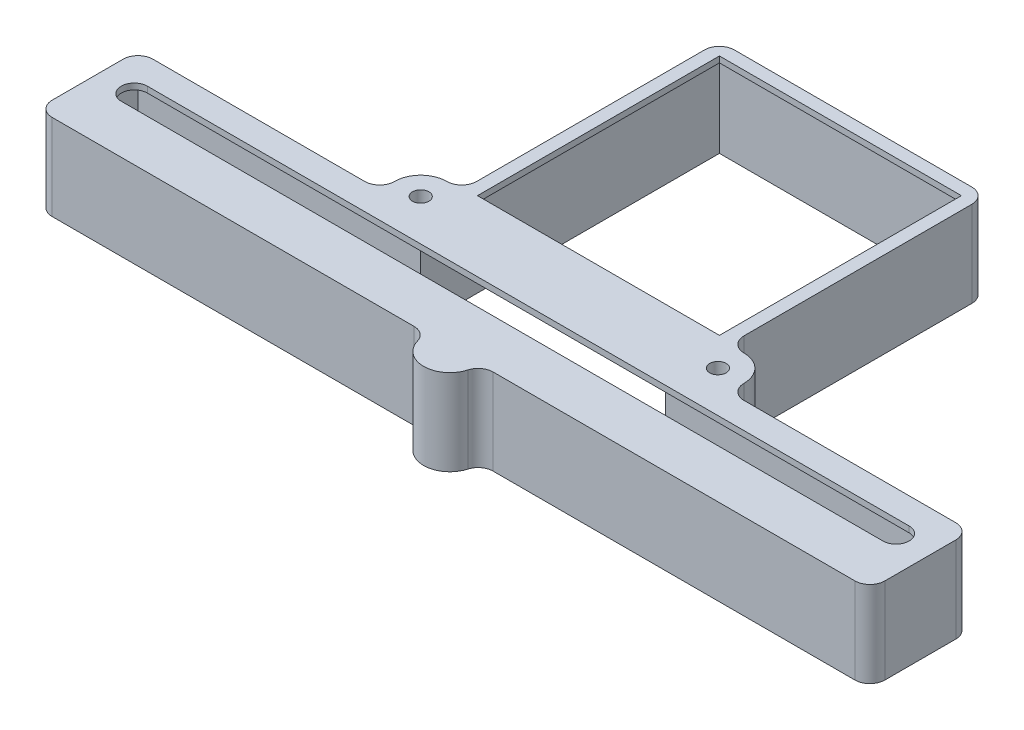
SolidWorks part; units mm, degrees
ref_plane "Front Plane" through (0, 0, 0) normal (0, 0, 1) x (1, 0, 0)
ref_plane "Top Plane" through (0, 0, 0) normal (0, 1, 0) x (1, 0, 0)
ref_plane "Right Plane" through (0, 0, 0) normal (1, 0, 0) x (0, 0, -1)
sketch "Sketch1" plane through (0, 0, 0) normal (0, 1, 0) x (1, 0, 0)
  line L0 (0, 36.3641) -> (0, -33.052) construction
  line L1 (-16.4, 25.25) -> (16.4, 25.25)
  line L2 (-16.4, 25.25) -> (-16.4, -25.25)
  line L3 (-16.4, -25.25) -> (16.4, -25.25)
  line L4 (16.4, 25.25) -> (16.4, -25.25)
  line L5 (-16.4, 25.25) -> (16.4, -25.25) construction
  line L6 (-16.4, -25.25) -> (16.4, 25.25) construction
  line L7 (-16.4, -25.25) -> (-16.4, -26.75) construction
  line L12 (-54.25, -14.75) -> (-55.75, -14.75) construction
  line L13 (-54.25, -14.75) -> (54.25, -14.75)
  line L14 (17.9, -26.75) -> (-17.9, -26.75)
  line L15 (17.9, -26.75) -> (17.9, 26.75)
  line L16 (17.9, 26.75) -> (-17.9, 26.75)
  line L17 (-17.9, -26.75) -> (-17.9, 26.75)
  line L18 (17.9, -26.75) -> (-17.9, 26.75) construction
  line L19 (17.9, 26.75) -> (-17.9, -26.75) construction
  line L20 (-16.4, 25.25) -> (-17.9, 25.25) construction
  line L21 (-16.4, 25.25) -> (-16.4, 26.75) construction
  line L22 (-54.25, -14.75) -> (-54.25, -25.25)
  line L23 (-54.25, -25.25) -> (54.25, -25.25)
  line L24 (54.25, -14.75) -> (54.25, -25.25)
  line L25 (-54.25, -14.75) -> (54.25, -25.25) construction
  line L26 (-54.25, -25.25) -> (54.25, -14.75) construction
  line L27 (-55.75, -13.25) -> (55.75, -13.25)
  line L28 (-55.75, -13.25) -> (-55.75, -26.75)
  line L29 (-55.75, -26.75) -> (55.75, -26.75)
  line L30 (55.75, -13.25) -> (55.75, -26.75)
  line L31 (-55.75, -13.25) -> (55.75, -26.75) construction
  line L32 (-55.75, -26.75) -> (55.75, -13.25) construction
  line L33 (-2, -27.25) -> (-3.5, -27.25) construction
  line L34 (-3.5, -27.25) -> (-3.5, -26.75)
  line L35 (3.5, -27.25) -> (3.5, -26.75)
  line L36 (-2, -27.25) -> (-2, -25.25)
  line L37 (2, -27.25) -> (2, -25.25)
  circle A0 centre (0, -27.25) radius 2
  circle A1 centre (0, -27.25) radius 3.5
  point P0 (0, 0)
  point P7 (0, -20)
  point P11 (0, -20)
  point P13 (0, 0)
  dimension "D6" = 4
  dimension "D1" = 32.8
  dimension "D2" = 50.5
  dimension "D3" = 1.5
  dimension "D4" = 108.5
  dimension "D5" = 10.5
extrude "Boss-Extrude1" add sketch "Sketch1" along normal blind 11.5 contours L17 L16 L15 L14 | L27 L30 L29 L28 | A1
sketch "Sketch2" plane through (0, 11.5, 0) normal (0, 1, 0) x (1, 0, 0)
  line L0 (0, 26.75) -> (0, -30.75) construction
  line L1 (17.9, 26.75) -> (-17.9, 26.75) construction
  line L3 (-16.2, 25.05) -> (-17.9, 25.05) construction
  line L4 (-16.2, -7.35) -> (16.2, -7.35)
  line L5 (-16.2, -7.35) -> (-16.2, 25.05)
  line L6 (-16.2, 25.05) -> (16.2, 25.05)
  line L7 (16.2, -7.35) -> (16.2, 25.05)
  line L8 (-16.2, -7.35) -> (16.2, 25.05) construction
  line L9 (-16.2, 25.05) -> (16.2, -7.35) construction
  line L10 (-17.9, -13.25) -> (-17.9, 26.75) construction
  line L11 (-16.2, 25.05) -> (-16.2, 26.75) construction
  arc A0 (-3.4641, -26.75) -> (3.4641, -26.75) centre (0, -27.25) ccw construction
  point P4 (0, 0)
  point P5 (0, 0)
  point P6 (0, 8.85)
  point P11 (0, -30.75)
  dimension "D1" = 32.4
extrude "Cut-Extrude1" cut sketch "Sketch2" against normal blind 8.7
sketch "Sketch3" plane through (0, 0, 0) normal (0, -1, 0) x (1, 0, 0)
  line L0 (-55.75, 20) -> (55.75, 20) construction
  line L1 (-55.75, 13.25) -> (-55.75, 26.75) construction
  line L2 (55.75, 13.25) -> (55.75, 26.75) construction
  line L3 (0, 30.75) -> (0, -26.75) construction
  line L4 (55.75, 26.75) -> (3.4641, 26.75) construction
  line L5 (17.9, -26.75) -> (-17.9, -26.75) construction
  line L6 (-54.25, 25.25) -> (-55.75, 25.25) construction
  line L7 (-54.25, 25.25) -> (54.25, 25.25)
  line L8 (-54.25, 25.25) -> (-54.25, 14.75)
  line L9 (-54.25, 14.75) -> (54.25, 14.75)
  line L10 (54.25, 25.25) -> (54.25, 14.75)
  line L11 (-54.25, 25.25) -> (54.25, 14.75) construction
  line L12 (-54.25, 14.75) -> (54.25, 25.25) construction
  line L13 (-54.25, 25.25) -> (-54.25, 26.75) construction
  line L14 (-2, 27.25) -> (-2, 25.25)
  line L15 (2, 27.25) -> (2, 25.25)
  arc A0 (3.4641, 26.75) -> (-3.4641, 26.75) centre (0, 27.25) ccw construction
  circle A1 centre (0, 27.25) radius 2
  point P12 (0, 20)
  dimension "D2" = 4
  dimension "D1" = 1.5
extrude "Cut-Extrude2" cut sketch "Sketch3" against normal offset from surface (10.7 mm away) 0.8 contours A1 | A1 L14 L7 | A1 L7 L15 | L10 L7 L8 L9 region at (0, 0, 20) region at (-1.5533, 0, 25.6967) region at (1.5533, 0, 25.6967) region at (0, 0, 27.25) up to face at (0, 11.5, -8.85)
sketch "Sketch4" plane through (0, 10.7, 0) normal (0, -1, 0) x (1, 0, 0)
  line L0 (-54.25, 18.5) -> (54.25, 18.5) construction
  line L1 (-54.25, 14.75) -> (-54.25, 25.25) construction
  line L2 (54.25, 25.25) -> (54.25, 14.75) construction
  line L3 (54.25, 14.75) -> (-54.25, 14.75) construction
  line L4 (51, 18.5) -> (-51, 18.5) construction
  line L5 (51, 16.75) -> (-51, 16.75)
  line L6 (51, 20.25) -> (-51, 20.25)
  arc A0 (51, 16.75) -> (51, 20.25) centre (51, 18.5) ccw
  arc A1 (-51, 20.25) -> (-51, 16.75) centre (-51, 18.5) ccw
  point P10 (0, 18.5)
  dimension "D1" = 3.75
  dimension "D2" = 3.5
  dimension "D3" = 102
extrude "Cut-Extrude3" cut sketch "Sketch4" against normal up to next
sketch "Sketch5" plane through (0, 0, 0) normal (0, -1, 0) x (1, 0, 0)
  line L0 (-17.9, -6.75) -> (17.9, -6.75) construction
  line L1 (-17.9, 13.25) -> (-17.9, -26.75) construction
  line L2 (17.9, 13.25) -> (17.9, -26.75) construction
  line L3 (-17.9, 13.25) -> (17.9, 13.25) construction
  line L4 (0, -26.75) -> (0, 13.25) construction
  line L5 (17.9, -26.75) -> (-17.9, -26.75) construction
  line L7 (-16.4, 14.75) -> (16.4, 14.75)
  line L8 (-16.4, 14.75) -> (-16.4, -25.25)
  line L9 (-16.4, -25.25) -> (16.4, -25.25)
  line L10 (16.4, 14.75) -> (16.4, -25.25)
  line L11 (-16.4, 14.75) -> (16.4, -25.25) construction
  line L12 (-16.4, -25.25) -> (16.4, 14.75) construction
  line L13 (54.25, 14.75) -> (-54.25, 14.75) construction
  line L14 (16.4, -25.25) -> (17.9, -25.25) construction
  line L15 (16.4, -25.25) -> (16.4, -26.75) construction
  point P14 (0, -5.25)
  dimension "D1" = 1.5
extrude "Cut-Extrude4" cut sketch "Sketch5" against normal up to surface (10.7 mm away) up to face at (0, 10.7, 18.5)
sketch "Sketch6" plane through (0, 10.7, 0) normal (0, -1, 0) x (1, 0, 0)
  line L0 (-16.4, -25.25) -> (-16.4, 14.75) construction
  line L1 (-16.4, 7.35) -> (16.4, 7.35)
  line L2 (-16.4, 7.35) -> (-16.4, 8.85)
  line L3 (-16.4, 8.85) -> (16.4, 8.85)
  line L4 (16.4, 7.35) -> (16.4, 8.85)
  line L5 (16.4, -25.25) -> (16.4, 14.75) construction
  line L7 (-16.2, 7.35) -> (16.2, 7.35) construction
  dimension "D1" = 1.5
extrude "Boss-Extrude2" add sketch "Sketch6" along normal offset from surface (7.7 mm away) 8.5 up to face at (0, 11.5, 18.5)
sketch "Sketch8" plane through (0, 11.5, 0) normal (0, 1, 0) x (1, 0, 0)
  line L0 (-55.75, -13.25) -> (-17.9, -13.25) construction
  line L2 (0, 31.5428) -> (0, -38.2394) construction
  line L3 (-19.9, -7.75) -> (-17.9, -7.75)
  line L4 (-17.9, -13.25) -> (-17.9, 26.75) construction
  line L5 (-23.4, -11.25) -> (-23.4, -13.25)
  line L6 (23.4, -11.25) -> (23.4, -13.25)
  line L7 (19.9, -7.75) -> (17.9, -7.75)
  line L8 (-23.4, -13.25) -> (-17.9, -13.25)
  line L9 (-17.9, -13.25) -> (-17.9, -7.75)
  line L10 (17.9, -13.25) -> (17.9, -7.75)
  line L11 (23.4, -13.25) -> (17.9, -13.25)
  circle A0 centre (-19.9, -11.25) radius 2
  circle A1 centre (19.9, -11.25) radius 2
  circle A2 centre (-19.9, -11.25) radius 3.5
  circle A3 centre (19.9, -11.25) radius 3.5
  circle A4 centre (-19.9, -11.25) radius 1.1
  circle A5 centre (19.9, -11.25) radius 1.1
  line M16 (-17.9, 26.75) -> (-17.9, -13.25)
  line M17 (-17.9, -13.25) -> (-55.75, -13.25)
  line M21 (55.75, -13.25) -> (17.9, -13.25)
  line M22 (17.9, -13.25) -> (17.9, 26.75)
  dimension "D1" = 4
  dimension "D3" = 1.5
  dimension "D2" = 2.2
extrude "Boss-Extrude5" add sketch "Sketch8" against normal up to surface (11.5 mm away) contours A2 L3 M16 | L9 A2 L8 A0 | A0 A4 | A0 L9 M17 | A2 L5 M17 | L11 A1 M22 | A1 A5 | A3 L10 A1 L11 | A3 L7 M22 | L6 A3 M21 region at (-18.8752, 11.5, 7.9848) region at (-18.3906, 11.5, 7.935) region at (-23.215, 11.5, 12.7594) region at (-18.5258, 11.5, 12.6242) region at (-18.3467, 11.5, 12.8033) region at (23.1652, 11.5, 12.2748) region at (23.215, 11.5, 12.7594) region at (18.3906, 11.5, 7.935) region at (18.3467, 11.5, 12.8033) region at (18.5258, 11.5, 12.6242) up to face at (0, 0, 13.8333)
fillet "Fillet1" radius 2 12 edges at (55.75, 5.75, 26.75) (55.75, 5.75, 13.25) (-55.75, 5.75, 26.75) (-55.75, 5.75, 13.25) (-17.9, 5.75, -26.75) (17.9, 5.75, -26.75) (-17.9, 5.75, 7.75) (-23.4, 5.75, 13.25) (23.4, 5.75, 13.25) (17.9, 5.75, 7.75) (-3.4641, 5.75, 26.75) (3.4641, 5.75, 26.75)
